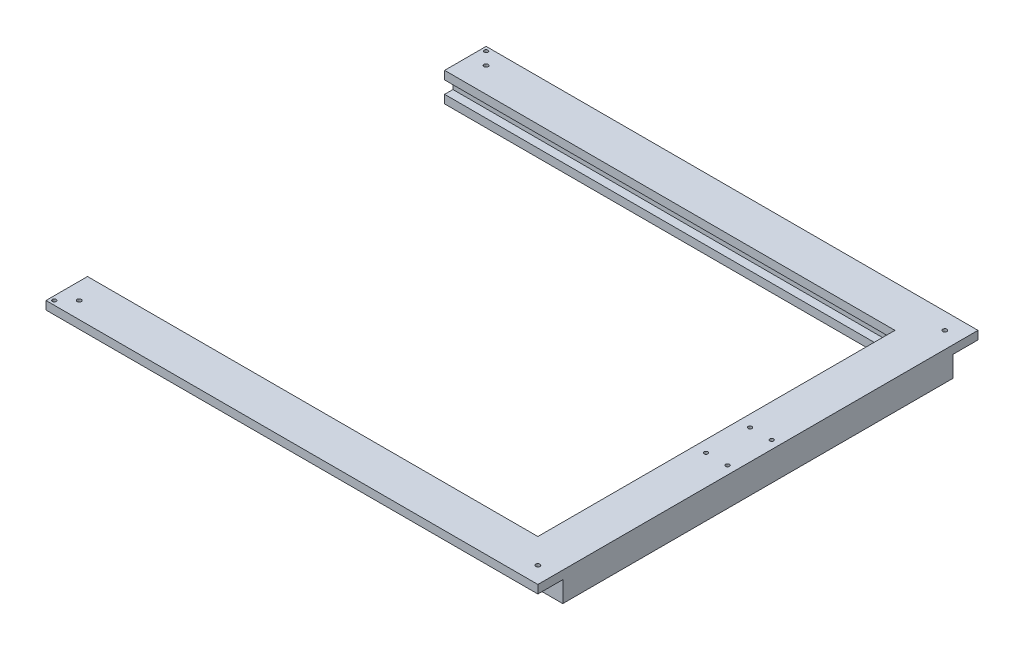
SolidWorks part; units mm, degrees
ref_plane "Спереди" through (0, 0, 0) normal (0, 0, 1) x (1, 0, 0)
ref_plane "Сверху" through (0, 0, 0) normal (0, 1, 0) x (1, 0, 0)
ref_plane "Справа" through (0, 0, 0) normal (1, 0, 0) x (0, 0, -1)
sketch "Эскиз1" plane through (0, 0, 0) normal (0, 1, 0) x (1, 0, 0)
  line L0 (50, -77.9215) -> (50, -607.9215)
  line L1 (-542.3, -77.9215) -> (50, -77.9215)
  line L2 (-542.3, -77.9215) -> (-542.3, -127.9215)
  line L3 (-542.3, -607.9215) -> (50, -607.9215)
  line L5 (-542.3, -127.9215) -> (0, -127.9215)
  line L7 (-542.3, -557.9215) -> (0, -557.9215)
  line L13 (-542.3, -557.9215) -> (-542.3, -607.9215)
  line L22 (0, -127.9215) -> (0, -557.9215)
  dimension "D1" = 592.3
  dimension "D12" = 50
  dimension "D2" = 530
  dimension "D3" = 50
  dimension "D4" = 50
  dimension "D9" = 50
  dimension "D8" = 77.9215
extrude "Бобышка-Вытянуть2" add sketch "Эскиз1" along normal blind 10
sketch "Эскиз2" plane through (0, 0, 0) normal (0, -1, 0) x (1, 0, 0)
  line L0 (-542.3, 127.9215) -> (0, 127.9215) construction
  line L5 (50, 607.9215) -> (50, 77.9215) construction
  line L6 (0, 557.9215) -> (-542.3, 557.9215) construction
  line L18 (50, 577.9215) -> (50, 107.9215)
  line L20 (10, 567.9215) -> (10, 117.9215)
  line L21 (-542.3, 77.9215) -> (-542.3, 127.9215) construction
  line L22 (50, 107.9215) -> (-542.3, 107.9215)
  line L24 (10, 117.9215) -> (-542.3, 117.9215)
  line L25 (-542.3, 107.9215) -> (-542.3, 117.9215)
  line L26 (-542.3, 557.9215) -> (-542.3, 607.9215) construction
  line L27 (50, 577.9215) -> (-542.3, 577.9215)
  line L29 (10, 567.9215) -> (-542.3, 567.9215)
  line L30 (-542.3, 577.9215) -> (-542.3, 567.9215)
  dimension "D1" = 40
  dimension "D2" = 10
  dimension "D3" = 10
  dimension "D4" = 10
  dimension "D5" = 10
extrude "Бобышка-Вытянуть3" add sketch "Эскиз2" along normal blind 15
sketch "Эскиз4" plane through (0, 10, 0) normal (0, 1, 0) x (1, 0, 0)
  line L0 (50, -77.9215) -> (-542.3, -77.9215) construction
  line L1 (-542.3, -77.9215) -> (-542.3, -127.9215) construction
  circle A0 centre (-522.3, -97.9215) radius 2.5
  dimension "D1" = 5
  dimension "D2" = 20
  dimension "D3" = 20
extrude "Вырез-Вытянуть1" cut sketch "Эскиз4" against normal through all
pattern_linear "Линейный массив2" count 2 spacing 552.3 along (1, 0, 0) count 2 spacing 490 along (0, 0, 1) of "Вырез-Вытянуть1"
sketch "Эскиз5" plane through (0, -15, 0) normal (0, -1, 0) x (1, 0, 0)
  line L8 (50, 577.9215) -> (-542.3, 577.9215)
  line L9 (-542.3, 577.9215) -> (-542.3, 557.9215)
  line L10 (-542.3, 557.9215) -> (0, 557.9215)
  line L11 (0, 557.9215) -> (0, 127.9215)
  line L12 (0, 127.9215) -> (-542.3, 127.9215)
  line L13 (-542.3, 127.9215) -> (-542.3, 107.9215)
  line L14 (-542.3, 107.9215) -> (50, 107.9215)
  line L15 (50, 107.9215) -> (50, 577.9215)
extrude "Бобышка-Вытянуть4" add sketch "Эскиз5" along normal blind 10
sketch "Эскиз6" plane through (0, -25, 0) normal (0, -1, 0) x (1, 0, 0)
  line L0 (40, 342.9215) -> (50, 342.9215) construction
  line L1 (40, 316.4215) -> (14, 316.4215) construction
  line L2 (40, 316.4215) -> (40, 369.4215) construction
  line L3 (40, 369.4215) -> (14, 369.4215) construction
  line L4 (14, 316.4215) -> (14, 369.4215) construction
  line L5 (50, 107.9215) -> (50, 577.9215) construction
  circle A1 centre (14, 369.4215) radius 2.25
  circle A2 centre (40, 369.4215) radius 2.25
  circle A3 centre (40, 316.4215) radius 2.25
  circle A4 centre (14, 316.4215) radius 2.25
  point P4 (50, 342.9215)
  point P6 (40, 342.9215)
  dimension "D4" = 4.5
  dimension "D1" = 53
  dimension "D2" = 26
  dimension "D3" = 10
extrude "Вырез-Вытянуть2" cut sketch "Эскиз6" against normal through all
sketch "Эскиз7" plane through (0, 0, 0) normal (0, -1, 0) x (1, 0, 0)
  line L0 (-542.3, 597.9215) -> (-532.3, 607.9215) construction
  line L1 (-542.3, 607.9215) -> (-532.3, 607.9215) construction
  line L2 (-542.3, 607.9215) -> (-542.3, 597.9215) construction
  line L3 (-542.3, 597.9215) -> (-532.3, 597.9215) construction
  line L4 (-532.3, 607.9215) -> (-532.3, 597.9215) construction
  line L5 (-542.3, 607.9215) -> (-532.3, 597.9215) construction
  line L6 (-532.3, 87.9215) -> (-542.3, 77.9215) construction
  line L7 (-542.3, 77.9215) -> (-532.3, 77.9215) construction
  line L8 (-542.3, 77.9215) -> (-542.3, 87.9215) construction
  line L9 (-542.3, 87.9215) -> (-532.3, 87.9215) construction
  line L10 (-532.3, 77.9215) -> (-532.3, 87.9215) construction
  line L11 (-542.3, 87.9215) -> (-532.3, 77.9215) construction
  circle A0 centre (-537.3, 602.9215) radius 2.25
  circle A1 centre (-537.3, 82.9215) radius 2.25
  point P12 (-537.3, 82.9215)
  dimension "D3" = 4.5
  dimension "D6" = 4.5
  dimension "D1" = 10
  dimension "D2" = 10
  dimension "D4" = 10
  dimension "D5" = 10
extrude "Вырез-Вытянуть3" cut sketch "Эскиз7" against normal through all
equation "\"Ширина груза\"= 420"
equation "\"Глубина груза\"= 490"
equation "\"Высота груза\"= 297"
equation "\"Ширина ячейки\"= \"Ширина груза\" + 10"
equation "\"Глубина ячейки\"= \"Глубина груза\" + 10"
equation "\"Высота ячейки\"= \"Высота груза\" + 10 + 13"
equation "\"Колво ячеек ширина\"= 2"
equation "\"Колво ячеек высота\"= 2"
equation "\"Толщина стенки\"= 10"
equation "\"Крепление дверцы\"= 5"
equation "\"Ширина рейки\"= \"Толщина шестерни\""
equation "\"Высота рейки\"= 20"
equation "\"Высота пола\"= 20"
equation "\"Колво полозьев\"= 5"
equation "\"Отступ рейки\"= 20"
equation "\"Глубина каретки\"= \"Глубина ячейки\" + 30 + \"Мотор Y высота корпуса\" + 20"
equation "\"Длинна рейки\"= ( \"Ширина ячейки\" + \"Толщина стенки\" + \"Крепление дверцы\" ) * \"Колво ячеек ширина\" + \"Ширина ячейки выгрузки\" * \"Колво выгрузки\" + \"Толщина стенки\""
equation "\"Отступ шпильки\"= 20"
equation "\"Диаметр шпильки\"= 5"
equation "\"Длинна шпильки\"= ( \"Высота ячейки\" + \"Толщина стенки\" + \"Высота пола\" ) * \"Колво ячеек высота\" + ( \"Толщина стенки\" + \"Отступ рейки\" ) * 2 "
equation "\"D2@Эскиз1\"=\"Ширина ячейки\" + \"Ширина пластины\" * 2 "
equation "\"D9@Эскиз1\"=\"Ширина пластины\""
equation "\"D3@Эскиз1\"=\"Ширина пластины\""
equation "\"D4@Эскиз1\"= \"Ширина пластины\""
equation "\"Ширина пластины\"= 50  "
equation "\"D1@Бобышка-Вытянуть2\"=\"Толщина стенки\""
equation "\"D1@Эскиз4\"= \"Диаметр шпильки\""
equation "\"D4@Линейный массив2\"=\"Ширина ячейки\" + \"Ширина пластины\" * 2  - \"Отступ шпильки\" * 2"
equation "\"D1@Эскиз1\"= \"Глубина каретки\""
equation "\"D3@Линейный массив2\"= \"Глубина каретки\" - \"Отступ шпильки\" * 2"
equation "\"D2@Эскиз4\"=\"Отступ шпильки\""
equation "\"D3@Эскиз4\"= \"Отступ шпильки\""
equation "\"D1@Эскиз2\"= \"Ширина пластины\" - \"Толщина стенки\""
equation "\"D2@Эскиз2\"= \"Толщина стенки\""
equation "\"D3@Эскиз2\"= \"Толщина стенки\""
equation "\"D4@Эскиз2\"= \"Толщина стенки\""
equation "\"D5@Эскиз2\"= \"Толщина стенки\""
equation "\"D1@Бобышка-Вытянуть4\"= \"Толщина стенки\""
equation "\"Вы\"=20"
equation "\"D1@Бобышка-Вытянуть3\"=\"Высота пола\" - 5"
equation "\"Высота зона выгрузки\"= \"Высота ячейки\" * 2 + \"Толщина стенки\" * 2"
equation "\"Колво выгрузки\"= 1"
equation "\"Ширина ячейки выгрузки\"= \"Ширина ячейки\" + \"Толщина стенки\" + \"Отступ крепления мотора фиксации\"*2"
equation "\"Отступ крепления мотора фиксации\" = 30"
equation "\"Мотор X ширина корпуса\"= 42.3"
equation "\"Мотор X высота корпуса\"= 42.3"
equation "\"Мотор X длина корпуса\"= 40"
equation "\"Мотор X вылет вала\"= 19.8"
equation "\"Мотор Y ширина корпуса\"= 42.3"
equation "\"Мотор Y высота корпуса\"= 42.3"
equation "\"Мотор Y длина корпуса\"= 48"
equation "\"Мотор Y вылет вала\"= 30"
equation "\"Мотор Z ширина корпуса\"= 42"
equation "\"Мотор Z высота корпуса\"= 42"
equation "\"Мотор Z длина корпуса\"= 40"
equation "\"Мотор Z вылет вала\"= 23"
equation "\"Мотор диаметр вала ПРЕДВ\"= 5"
equation "\"Мотор шаг крепления ПРЕДВ\"= 31"
equation "\"Мотор диаметр отверстий ПРЕДВ\"= 3"
equation "\"Мотор глубина отверстий ПРЕДВ\"= 4.5"
equation "\"Мотор диаметр буртика ПРЕДВ\"= 22"
equation "\"Мотор высота буртика ПРЕДВ\"= 2"
equation "\"Мотор диаметр шкива ПРЕДВ\"= 16"
equation "\"Мотор длина шкива ПРЕДВ\"= 12"
equation "\"Мотор отступ шкива ПРЕДВ\"= 5"
equation "\"Мотор X шаг градусов\"= 1.8"
equation "\"Мотор X ток А\"= 1.5"
equation "\"Мотор X сопротивление Ом\"= 1.3"
equation "\"Мотор X индуктивность мГн\"= 2"
equation "\"Мотор Y шаг градусов\"= 1.8"
equation "\"Мотор Y ток А\"= 2.2"
equation "\"Мотор Y сопротивление Ом\"= 0.9"
equation "\"Мотор Y индуктивность мГн\"= 2"
equation "\"Мотор Z шаг градусов\"= 1.8"
equation "\"Мотор Z ток А\"= 1"
equation "\"Мотор Z сопротивление Ом\"= 4"
equation "\"Мотор Z индуктивность мГн\"= 8"
equation "\"Мотор Y диаметр ротора\"= 25.78"
